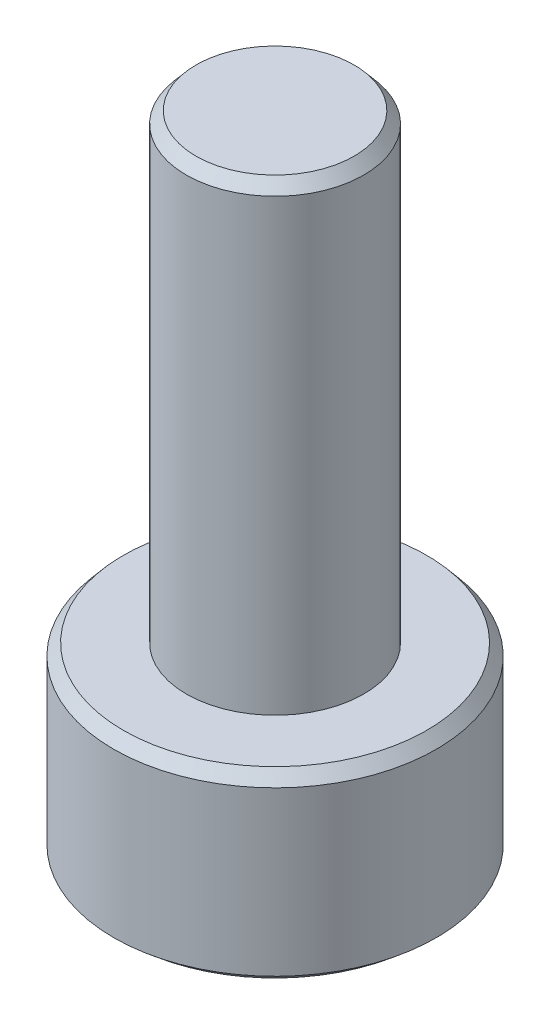
SolidWorks part; units mm, degrees
ref_plane "Front Plane" through (0, 0, 0) normal (0, 0, 1) x (1, 0, 0)
ref_plane "Top Plane" through (0, 0, 0) normal (0, 1, 0) x (1, 0, 0)
ref_plane "Right Plane" through (0, 0, 0) normal (1, 0, 0) x (0, 0, -1)
sketch "Sketch1" plane through (0, 0, 0) normal (0, 1, 0) x (1, 0, 0)
  circle A0 centre (0, 0) radius 3.5
  dimension "D1" = 7
extrude "Boss-Extrude1" add sketch "Sketch1" along normal blind 4
sketch "Sketch2" plane through (0, 4, 0) normal (0, 1, 0) x (1, 0, 0)
  circle A0 centre (0, 0) radius 1.925
  dimension "D1" = 3.85
extrude "Boss-Extrude2" add sketch "Sketch2" along normal blind 10
sketch "Sketch3" plane through (0, 0, 0) normal (0, -1, 0) x (1, 0, 0)
  line L1 (0, 2.3719) -> (-2.0541, 1.186)
  line L2 (-2.0541, 1.186) -> (-2.0541, -1.186)
  line L3 (-2.0541, -1.186) -> (0, -2.3719)
  line L4 (0, -2.3719) -> (2.0541, -1.186)
  line L5 (2.0541, -1.186) -> (2.0541, 1.186)
  line L6 (2.0541, 1.186) -> (0, 2.3719)
  circle A0 centre (0, 0) radius 2.0541 construction
extrude "Cut-Extrude1" cut sketch "Sketch3" against normal blind 2
chamfer "Chamfer1" distance 0.25 angle 40 9 edges at (-2.0541, 0, 0) (-1.0271, 0, -1.7789) (1.0271, 0, -1.7789) (2.0541, 0, 0) (1.0271, 0, 1.7789) (-1.0271, 0, 1.7789) (0, 0, 3.5) (0, 4, 3.5) (0, 14, 1.925) first distance on face at (0, 0, 0) first distance on face at (0, 4, 3.5) first distance on face at (0, 14, 1.925)
